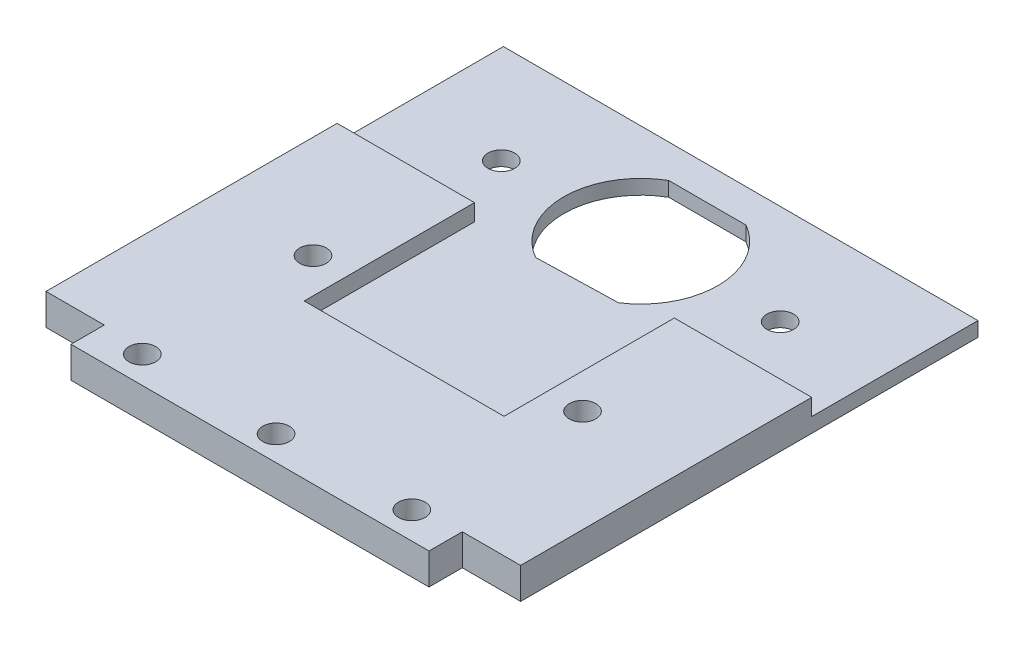
SolidWorks part; units mm, degrees
ref_plane "Ebene vorne" through (0, 0, 0) normal (0, 0, 1) x (1, 0, 0)
ref_plane "Ebene oben" through (0, 0, 0) normal (0, 1, 0) x (1, 0, 0)
ref_plane "Ebene rechts" through (0, 0, 0) normal (1, 0, 0) x (0, 0, -1)
sketch "Skizze1" plane through (0, 0, 0) normal (0, 1, 0) x (1, 0, 0)
  line L0 (0, 4) -> (7, 4)
  line L1 (7, 0) -> (17.7787, 0)
  line L2 (0, 4) -> (0, 58.9339)
  line L3 (0, 58.9339) -> (57, 58.9339)
  line L4 (57, 4) -> (57, 58.9339)
  line L5 (7, 4) -> (7, 0)
  line L9 (50, 0) -> (50, 4)
  line L10 (50, 4) -> (57, 4)
  line L11 (38.7787, 0) -> (50, 0)
  line L12 (17.7787, 0) -> (38.7787, 0)
  dimension "D1" = 57
  dimension "D3" = 7
  dimension "D4" = 4
  dimension "D7" = 4
  dimension "D8" = 7
extrude "Aufsatz-Linear austragen1" add sketch "Skizze1" against normal blind 3.75
sketch "Skizze16" plane through (0, 0, 0) normal (0, 1, 0) x (1, 0, 0)
  line L0 (57, 58.9339) -> (57, 38.9637)
  line L1 (57, 4) -> (57, 58.9339) construction
  line L2 (57, 38.9637) -> (0, 38.9637)
  line L3 (0, 58.9339) -> (0, 4) construction
  line L4 (0, 38.9637) -> (0, 58.9339)
  line L5 (0, 58.9339) -> (57, 58.9339)
extrude "Schnitt-Linear austragen6" cut sketch "Skizze16" against normal blind 2
sketch "Skizze3" plane through (0, -2, 0) normal (0, 1, 0) x (1, 0, 0)
  line L0 (57, 58.9339) -> (0, 58.9339) construction
  line L1 (33.5654, 39.1941) -> (23.8565, 38.9339)
  line L2 (57, 4) -> (57, 38.9637) construction
  line L3 (38.5, 38.9339) -> (18.5, 38.9339) construction
  line L4 (33.1435, 54.9339) -> (23.8565, 54.9339)
  line L5 (18.5, 54.9339) -> (38.5, 54.9339) construction
  arc A0 (33.5654, 39.1941) -> (33.1435, 54.9339) centre (28.5, 46.9339) ccw
  arc A1 (23.8565, 54.9339) -> (23.8565, 38.9339) centre (28.5, 46.9339) ccw
  dimension "D3" = 18.5
  dimension "D1" = 12
  dimension "D2" = 28.5
extrude "Schnitt-Linear austragen1" cut sketch "Skizze3" against normal blind 2
ref_plane "Ebene1" through (28.5, 0, 0) normal (-1, 0, 0) x (0, 0, 1)
sketch "Skizze10" plane through (0, -2, 0) normal (0, 1, 0) x (1, 0, 0)
  line L1 (57, 58.9339) -> (0, 58.9339) construction
  line L2 (57, 4) -> (57, 38.9637) construction
  line L3 (0, 38.9637) -> (0, 4) construction
  circle A0 centre (45.25, 46.9339) radius 1.6
  circle A1 centre (11.75, 46.9339) radius 1.6
  dimension "D5" = 3.2
  dimension "D1" = 12
  dimension "D2" = 12
  dimension "D3" = 11.75
  dimension "D4" = 11.75
extrude "Schnitt-Linear austragen3" cut sketch "Skizze10" against normal blind 3.2
ref_plane "Ebene2" through (0, 0, -20.9339) normal (0, 0, -1) x (-1, 0, 0)
sketch "Skizze17" plane through (0, 0, 0) normal (0, 1, 0) x (1, 0, 0)
  line L0 (7, 0) -> (50, 0) construction
  line L1 (7, 0) -> (50, 0) construction
  line L2 (57, 4) -> (57, 38.9637) construction
  line L3 (0, 38.9637) -> (0, 4) construction
  circle A0 centre (44.6847, 3.25) radius 1.6
  circle A1 centre (44.6847, 23.75) radius 1.6
  circle A2 centre (12.3153, 3.25) radius 1.6
  circle A3 centre (12.3153, 23.75) radius 1.6
  dimension "D1" = 3.2
  dimension "D2" = 3.2
  dimension "D3" = 3.2
  dimension "D4" = 3.25
  dimension "D5" = 20.5
  dimension "D6" = 20.5
  dimension "D7" = 3.25
  dimension "D8" = 12.3153
  dimension "D9" = 12.3153
extrude "Schnitt-Linear austragen7" cut sketch "Skizze17" against normal blind 4
sketch "Skizze18" plane through (0, 0, 0) normal (0, 1, 0) x (1, 0, 0)
  line L0 (0, 38.9637) -> (57, 38.9637) construction
  line L1 (40.5, 38.9637) -> (16.5, 38.9637)
  line L2 (40.5, 38.9637) -> (40.5, 18.5122)
  line L3 (40.5, 18.5122) -> (16.5, 18.5122)
  line L4 (16.5, 38.9637) -> (16.5, 18.5122)
  line L5 (40, 19.0386) -> (40, 38.5386) construction
  dimension "D1" = 20.4515
  dimension "D2" = 24
  dimension "D3" = 0.5
extrude "Schnitt-Linear austragen8" cut sketch "Skizze18" against normal blind 2
ref_plane "Ebene3" through (33.1435, -2, -54.9339) normal (0, 1, 0) x (1, 0, 0)
sketch "Skizze19" plane through (0, 0, 0) normal (0, 1, 0) x (1, 0, 0)
  circle A0 centre (28.6325, 2.9955) radius 1.6
extrude "Schnitt-Linear austragen9" cut sketch "Skizze19" against normal blind 10
